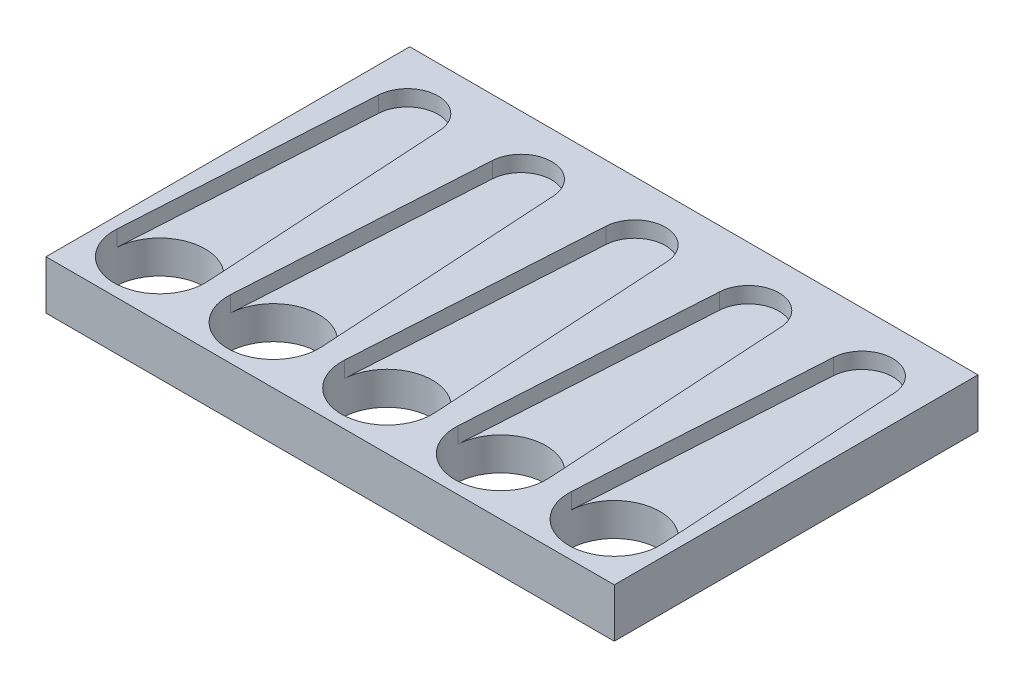
SolidWorks part; units mm, degrees
ref_plane "Front Plane" through (0, 0, 0) normal (0, 0, 1) x (1, 0, 0)
ref_plane "Top Plane" through (0, 0, 0) normal (0, 1, 0) x (1, 0, 0)
ref_plane "Right Plane" through (0, 0, 0) normal (1, 0, 0) x (0, 0, -1)
sketch "Sketch1" plane through (0, 0, 0) normal (0, 1, 0) x (1, 0, 0)
  line L0 (5, 32) -> (5, 0) construction
  line L1 (0, 0) -> (10, 0)
  line L2 (0, 0) -> (0, 32)
  line L3 (0, 32) -> (10, 32)
  line L4 (10, 0) -> (10, 32)
  line L5 (5, 29.5) -> (5, 1) construction
  line L6 (2.3048, 26.961) -> (1.0071, 5.2385)
  line L7 (7.6952, 26.961) -> (8.9929, 5.2385)
  circle A0 centre (5, 5) radius 4
  circle A1 centre (5, 26.8) radius 2.7
  dimension "D3" = 8
  dimension "D5" = 28.5
  dimension "D6" = 5.4
  dimension "D1" = 10
  dimension "D2" = 32
  dimension "D4" = 5
extrude "Boss-Extrude1" add sketch "Sketch1" along normal blind 1.4 contours L1 L4 L3 L2 A1 L7 A0 L6 region at (0.3353, 0, -16)
extrude "Boss-Extrude2" add sketch "Sketch1<3>" against normal blind 2.9 contours A1 L6 A0 L7 | A1 | L1 L4 L3 L2 A1 L7 A0 L6 region at (0.3353, 0, -16) region at (5, 0, -16.0499) region at (5, 0, -26.8)
sketch "Sketch1<3>" plane through (0, 0, 0) normal (0, 1, 0) x (1, 0, 0) same geometry as "Sketch1"
pattern_linear "LPattern1" count 5 spacing 10 along (1, 0, 0) of "Boss-Extrude2", "Boss-Extrude1"
